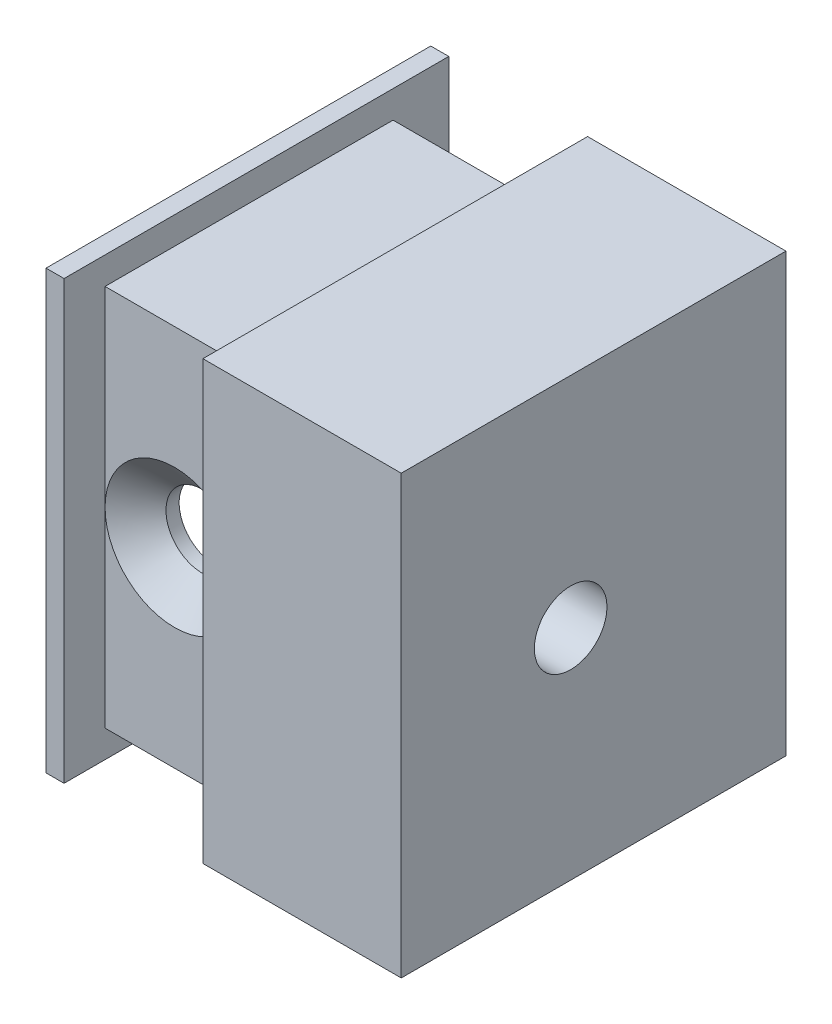
SolidWorks part; units mm, degrees
ref_plane "Top Plane" through (0, 0, 0) normal (0, 0, 1) x (1, 0, 0)
ref_plane "Right Plane" through (0, 0, 0) normal (0, 1, 0) x (1, 0, 0)
ref_plane "Front Plane" through (0, 0, 0) normal (1, 0, 0) x (0, 0, -1)
ref_axis "x-axis" through (-88.99, 0, 0) along (1, 0, 0)
ref_axis "y-axis" through (0, -55, 0) along (0, 1, 0)
ref_axis "z-axis" through (0, 0, 55) along (0, 0, -1)
sketch "Sketch1" plane through (0, 0, 0) normal (0, 1, 0) x (1, 0, 0)
  line L0 (0, 0) -> (-41.275, 0)
  line L5 (-41.275, 0) -> (-41.275, -14.859)
  line L6 (-41.275, -14.859) -> (-9.525, -14.859)
  line L7 (-9.525, -14.859) -> (-9.525, -35.179)
  line L8 (-9.525, -35.179) -> (-41.275, -35.179)
  line L9 (-41.275, -35.179) -> (-41.275, -44.704)
  line L10 (-41.275, -44.704) -> (0, -44.704)
  line L11 (0, -44.704) -> (0, 0)
  dimension "D1" = 31.75
  dimension "D2" = 31.75
  dimension "D3" = 14.859
  dimension "D4" = 9.525
  dimension "D5" = 9.525
  dimension "D6" = 20.32
extrude "Boss-Extrude1" add sketch "Sketch1" along normal blind 38.1
sketch "Sketch2" plane through (0, 38.1, 0) normal (0, 1, 0) x (-1, 0, 0)
  line L0 (41.275, 44.704) -> (41.275, 0)
  line L8 (0, 44.704) -> (0, 0)
  line L9 (0, 0) -> (41.275, 0)
  line L10 (41.275, 0) -> (41.275, 14.859)
  line L11 (41.275, 14.859) -> (9.525, 14.859)
  line L12 (9.525, 14.859) -> (9.525, 35.179)
  line L13 (9.525, 35.179) -> (41.275, 35.179)
  line L14 (41.275, 35.179) -> (41.275, 44.704)
  line L15 (41.275, 44.704) -> (0, 44.704)
  line L16 (0, 44.704) -> (0, 0)
  line L17 (0, 0) -> (41.275, 0)
  line L23 (41.275, 44.704) -> (0, 44.704)
  dimension "D1" = 0
extrude "End Caps" add sketch "Sketch2" along normal blind 6.35
ref_plane "Mid Plane Vertical" through (0, 19.05, 0) normal (0, -1, 0) x (-1, 0, 0)
mirror "Mirror1" about plane through (0, 19.05, 0) normal (0, -1, 0) of "End Caps"
hole_wizard "Channel Countersink-PRE" positions "Sketch4" profile "Sketch5" countersink size "5/16" standard "ANSI Inch"
sketch "Sketch4" plane through (0, 0, 44.704) normal (0, 0, 1) x (1, 0, 0)
  line L0 (-41.275, 44.45) -> (0, -6.35) construction
  line L2 (-41.275, -6.35) -> (0, 44.45) construction
  line L3 (0, 19.05) -> (-41.275, 19.05) construction
  line L4 (0, 44.45) -> (0, -6.35) construction
  line L5 (-41.275, 44.45) -> (-41.275, -6.35) construction
  point P0 (-31.115, 19.05)
  point P25 (0, 0)
  point P26 (-18.1943, 19.05)
  point P28 (0, 0)
  dimension "D1" = 10.16
sketch "Sketch5" plane through (-31.115, 19.05, 44.704) normal (1, 0, 0) x (0, -1, 0)
  line L0 (0, 0) -> (0, 12.0585)
  line L1 (0, 12.0585) -> (4.2164, 9.525)
  line L2 (4.2164, 9.525) -> (4.2164, 3.2289)
  line L3 (4.2164, 3.2289) -> (8.0645, 0)
  line L5 (8.0645, 0) -> (0, 0)
  line L6 (-4.2164, 3.2289) -> (-8.0645, 0) construction
  line L10 (0, 12.0585) -> (-4.2164, 9.525) construction
  line L11 (0, -6.35) -> (0, 107.95) construction
  dimension "Hole Dia." = 8.4328
  dimension "Hole Depth" = 9.525
  dimension "Near C'Sink Dia." = 16.129
  dimension "Near C'Sink Angle" = 100
  dimension "Drill Angle" = 118
hole_wizard "Mounting Countersink" positions "Sketch10" profile "Sketch11" countersink size "5/16" standard "ANSI Inch" end condition through all
sketch "Sketch10" plane through (-9.525, 0, 0) normal (-1, 0, 0) x (0, 0, 1)
  line L0 (-11.176, 19.05) -> (11.176, 19.05) construction
  line L1 (35.179, 38.1) -> (14.859, 0) construction
  line L3 (35.179, 0) -> (14.859, 38.1) construction
  point P0 (25.019, 19.05)
  point P18 (19.05, 19.05)
sketch "Sketch11" plane through (-9.525, 19.05, 25.019) normal (0, 1, 0) x (0, 0, 1)
  line L0 (0, 0) -> (0, 9.525)
  line L1 (0, 9.525) -> (4.2164, 9.525)
  line L2 (4.2164, 9.525) -> (4.2164, 3.2289)
  line L3 (4.2164, 3.2289) -> (8.0645, 0)
  line L5 (8.0645, 0) -> (0, 0)
  line L6 (-4.2164, 3.2289) -> (-8.0645, 0) construction
  line L11 (0, -6.35) -> (0, 107.95) construction
  dimension "Thru Hole Dia." = 8.4328
  dimension "Thru Hole Depth" = 9.525
  dimension "Near C'Sink Dia." = 16.129
  dimension "Near C'Sink Angle" = 100
sketch "Sketch13" plane through (0, -6.35, 0) normal (0, -1, 0) x (1, 0, 0)
  line L0 (-23.0505, 44.704) -> (-23.0505, 39.9415)
  line L1 (-41.275, 44.704) -> (0, 44.704) construction
  line L2 (-23.0505, 39.9415) -> (-39.1795, 39.9415)
  line L3 (-39.1795, 39.9415) -> (-39.1795, 44.704)
  line L5 (-9.525, 35.179) -> (-41.275, 35.179) construction
  line L6 (-9.525, 35.179) -> (-41.275, 35.179) construction
  line L7 (-25.4, 35.179) -> (-25.4, 44.704) construction
  line L8 (-23.0505, 44.704) -> (-39.1795, 44.704) construction
  line L9 (-23.0505, 44.704) -> (-39.1795, 44.704)
  point P10 (-25.4, 39.9415)
  point P13 (0, 0)
  point P14 (0, 0)
extrude "Channel Top and Bottom" cut sketch "Sketch13" against normal through all
hole_wizard "Channel Countersink" positions "Sketch14" profile "Sketch15" countersink size "5/16" standard "ANSI Inch"
sketch "Sketch14" plane through (0, 0, 39.9415) normal (0, 0, 1) x (1, 0, 0)
  point P0 (-31.115, 19.05)
  point P3 (0, 0)
  point P4 (0, 0)
  point P5 (-23.8125, 19.05)
sketch "Sketch15" plane through (-31.115, 19.05, 39.9415) normal (1, 0, 0) x (0, -1, 0)
  line L0 (0, 0) -> (0, 7.296)
  line L1 (0, 7.296) -> (4.2164, 4.7625)
  line L2 (4.2164, 4.7625) -> (4.2164, 3.2289)
  line L3 (4.2164, 3.2289) -> (8.0645, 0)
  line L5 (8.0645, 0) -> (0, 0)
  line L6 (-4.2164, 3.2289) -> (-8.0645, 0) construction
  line L10 (0, 7.296) -> (-4.2164, 4.7625) construction
  line L11 (0, -6.35) -> (0, 107.95) construction
  dimension "Hole Dia." = 8.4328
  dimension "Hole Depth" = 4.7625
  dimension "Near C'Sink Dia." = 16.129
  dimension "Near C'Sink Angle" = 100
  dimension "Drill Angle" = 118
ref_plane "Mid Plane Horizontal" through (0, 0, 25.019) normal (0, 0, -1) x (-1, 0, 0)
sketch "Sketch16" plane through (0, 0, 0) normal (0, 0, -1) x (1, 0, 0)
  line L1 (-39.1795, 6.35) -> (-39.1795, 3.175)
  line L3 (-39.1795, 3.175) -> (-23.0505, 3.175)
  line L6 (-41.275, 0) -> (-9.525, 0) construction
  line L7 (-41.275, 0) -> (-9.525, 0) construction
  line L8 (-31.115, 6.35) -> (-31.115, 0) construction
  line L9 (-39.1795, 6.35) -> (-23.0505, 6.35) construction
  line L10 (-39.1795, 6.35) -> (-23.0505, 6.35)
  line L11 (-23.0505, 3.175) -> (-23.0505, 6.35)
  point P1 (0, 0)
  point P4 (-31.115, 3.175)
  point P6 (-31.115, 6.35)
extrude "Channel Left Right" cut sketch "Sketch16" against normal through all
sketch "Sketch17" plane through (0, 44.45, 0) normal (0, 1, 0) x (-1, 0, 0)
  line L0 (23.0505, 0) -> (23.0505, 6.477)
  line L1 (0, 0) -> (41.275, 0) construction
  line L2 (23.0505, 6.477) -> (39.1795, 6.477)
  line L3 (39.1795, 6.477) -> (39.1795, 0)
  line L5 (23.0505, 39.9415) -> (23.0505, 0) construction
  line L6 (39.1795, 39.9415) -> (23.0505, 39.9415) construction
  line L7 (39.1795, 39.9415) -> (23.0505, 39.9415) construction
  line L8 (39.1795, 39.9415) -> (39.1795, 0) construction
  line L10 (23.0505, 0) -> (39.1795, 0)
  line L11 (41.275, 15.113) -> (9.525, 15.113)
  line L12 (41.275, 15.113) -> (9.525, 15.113) construction
  point P10 (31.115, 6.477)
  dimension "D1" = 0.254
  dimension "D2" = 8.636
extrude "Cut-Extrude3" cut sketch "Sketch17" against normal through all
mirror "Mirror3" about plane through (0, 19.05, 0) normal (0, -1, 0) of "Channel Left Right"
hole_wizard "5/16 (0.47) Diameter Hole1" positions "Sketch18" profile "Sketch20" hole size "5/16" standard "ANSI Inch" end condition up to next
sketch "Sketch18" plane through (0, 0, 0) normal (0, 0, 1) x (1, 0, 0)
  circle A0 centre (-31.115, 19.05) radius 4.2164 construction
  circle A1 centre (-31.115, 19.05) radius 4.2164
  point P0 (-31.115, 19.05)
  point P6 (-31.115, 19.05)
sketch "Sketch20" plane through (-31.115, 19.05, 0) normal (1, 0, 0) x (0, 1, 0)
  line L0 (0, 0) -> (0, 14.859)
  line L1 (0, 14.859) -> (5.969, 14.859)
  line L2 (5.969, 14.859) -> (5.969, 0)
  line L5 (5.969, 0) -> (0, 0)
  line L11 (0, -6.35) -> (0, 107.95) construction
  dimension "Thru Hole Dia." = 11.938
  dimension "Thru Hole Depth" = 14.859
